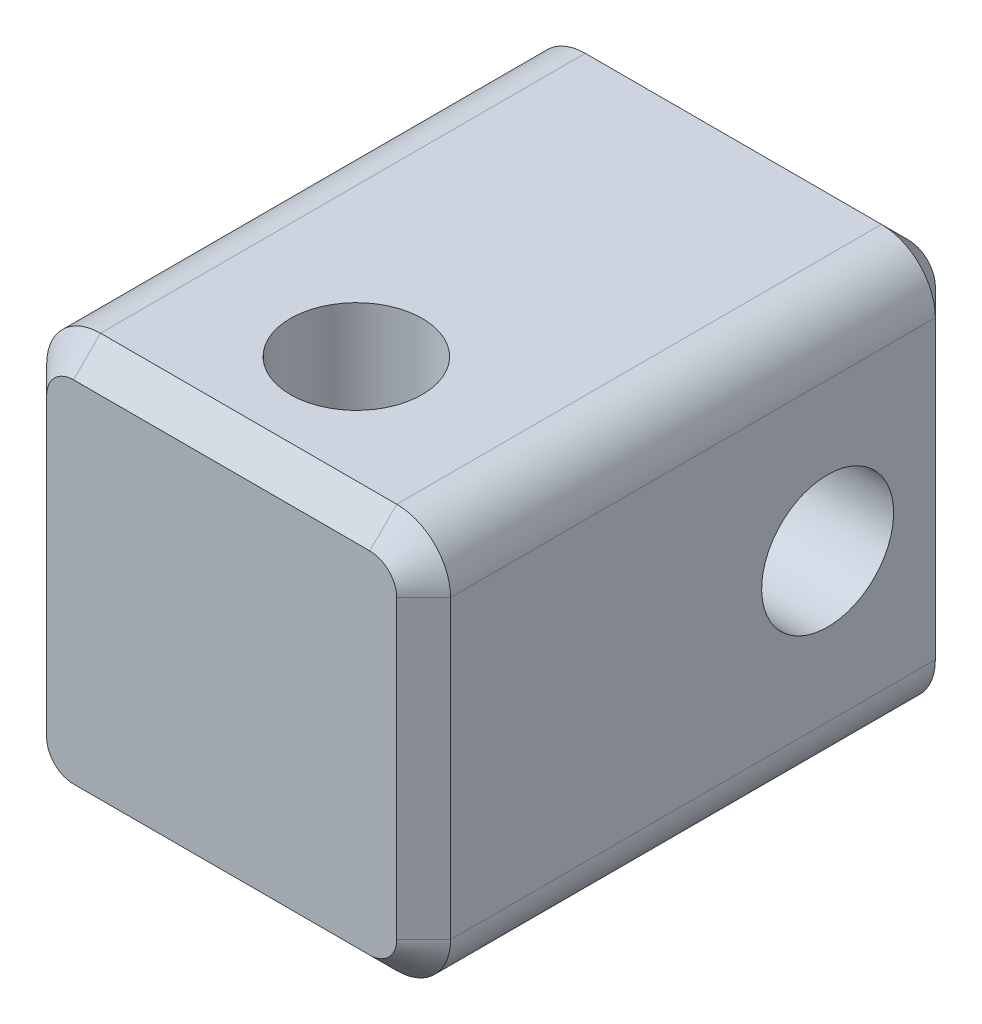
SolidWorks part; units mm, degrees
ref_plane "正面(Front)" through (0, 0, 0) normal (0, 0, 1) x (1, 0, 0)
ref_plane "平面(Top)" through (0, 0, 0) normal (0, 1, 0) x (1, 0, 0)
ref_plane "右側面(Right)" through (0, 0, 0) normal (1, 0, 0) x (0, 0, -1)
sketch "ｽｹｯﾁ1" plane through (0, 0, 0) normal (0, 0, 1) x (1, 0, 0)
  line L1 (-7.5, 7.5) -> (7.5, 7.5)
  line L2 (-7.5, 7.5) -> (-7.5, -7.5)
  line L3 (-7.5, -7.5) -> (7.5, -7.5)
  line L4 (7.5, 7.5) -> (7.5, -7.5)
  line L5 (-7.5, 7.5) -> (7.5, -7.5) construction
  line L6 (-7.5, -7.5) -> (7.5, 7.5) construction
  point P0 (0, 0)
  dimension "D1" = 15
  dimension "D2" = 15
extrude "ﾎﾞｽ - 押し出し1" add sketch "ｽｹｯﾁ1" along normal blind 20
sketch "ｽｹｯﾁ2" plane through (7.5, 0, 0) normal (1, 0, 0) x (0, 0, -1)
  line L0 (0, 0) -> (-23.2092, 0) construction
  line L1 (0, -7.5) -> (0, 7.5) construction
  circle A0 centre (-5, 0) radius 2.45
  dimension "D1" = 5
  dimension "D2" = 4.9
extrude "ｶｯﾄ - 押し出し1" cut sketch "ｽｹｯﾁ2" against normal through all
sketch "ｽｹｯﾁ3" plane through (0, 7.5, 0) normal (0, 1, 0) x (1, 0, 0)
  line L0 (0, 0) -> (0, -20) construction
  line L1 (7.5, -20) -> (-7.5, -20) construction
  circle A0 centre (0, -15) radius 2.45
  dimension "D1" = 4.9
  dimension "D2" = 5
extrude "ｶｯﾄ - 押し出し2" cut sketch "ｽｹｯﾁ3" against normal through all
fillet "ﾌｨﾚｯﾄ1" radius 2 4 edges at (7.5, -7.5, 10) (-7.5, -7.5, 10) (-7.5, 7.5, 10) (7.5, 7.5, 10)
chamfer "面取り1" distance 1 angle 45 16 edges at (-6.9142, -6.9142, 20) (-7.5, 0, 20) (-6.9142, 6.9142, 20) (0, 7.5, 20) (6.9142, 6.9142, 20) (7.5, 0, 20) (6.9142, -6.9142, 20) (0, -7.5, 20) (6.9142, 6.9142, 0) (0, 7.5, 0) (-6.9142, 6.9142, 0) (-7.5, 0, 0) (-6.9142, -6.9142, 0) (0, -7.5, 0) (6.9142, -6.9142, 0) (7.5, 0, 0)
ref_plane "平面1" through (0, 0, 0) normal (0, 1, 0) x (1, 0, 0)
ref_axis "軸1" through (0, -7.5, 15) along (0, 1, 0)
ref_point "点1"
ref_plane "平面2" through (0, 0, 0) normal (1, 0, 0) x (0, 0, -1)
ref_axis "軸2" through (-7.5, 0, 5) along (1, 0, 0)
ref_point "joint"
